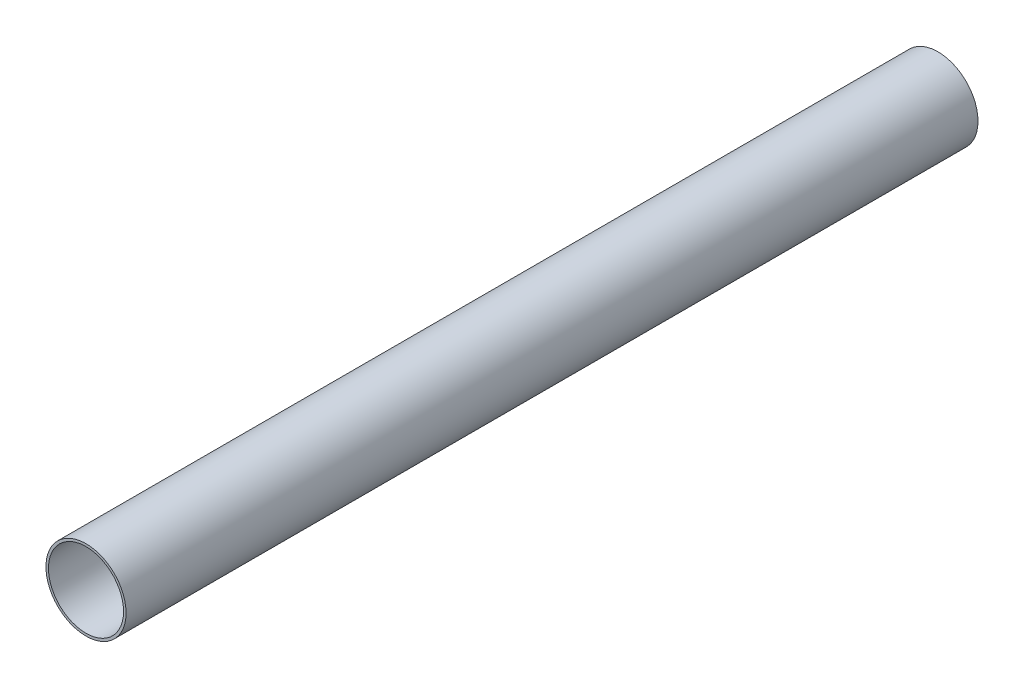
SolidWorks part; units mm, degrees
material "PC High Viscosity"
ref_plane "Front Plane" through (0, 0, 0) normal (0, 0, 1) x (1, 0, 0)
ref_plane "Top Plane" through (0, 0, 0) normal (0, 1, 0) x (1, 0, 0)
ref_plane "Right Plane" through (0, 0, 0) normal (1, 0, 0) x (0, 0, -1)
sketch "Sketch1" plane through (0, 0, 0) normal (0, 0, 1) x (1, 0, 0)
  circle A0 centre (0, 0) radius 23.8125
  circle A1 centre (0, 0) radius 25.4
  dimension "D1" = 50.8
  dimension "D2" = 47.625
extrude "Boss-Extrude1" add sketch "Sketch1" along normal mid plane 540.2
equation "\"D1@Boss-Extrude1\"=21.125in+3.625mm"
